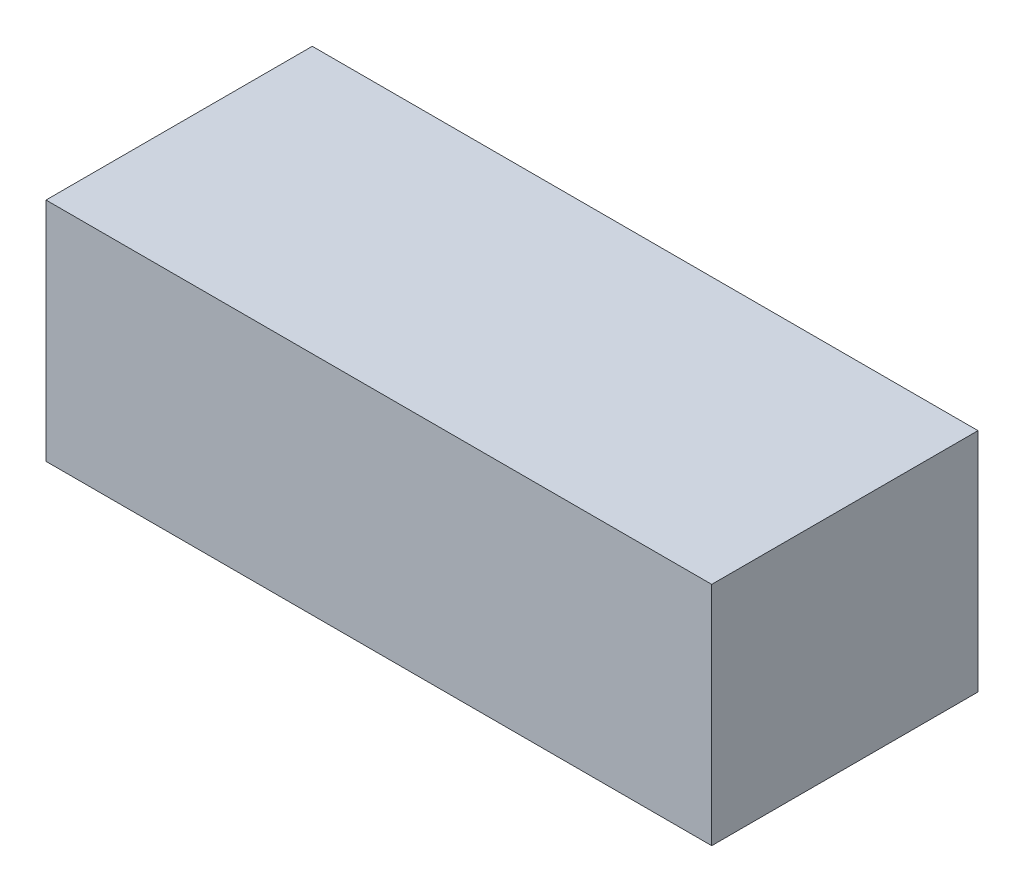
SolidWorks part; units mm, degrees
ref_plane "Front Plane" through (0, 0, 0) normal (0, 0, 1) x (1, 0, 0)
ref_plane "Top Plane" through (0, 0, 0) normal (0, 1, 0) x (1, 0, 0)
ref_plane "Right Plane" through (0, 0, 0) normal (1, 0, 0) x (0, 0, -1)
sketch "Sketch1" plane through (0, 0, 0) normal (0, 1, 0) x (1, 0, 0)
  line L1 (-25, -10) -> (25, -10)
  line L2 (-25, -10) -> (-25, 10)
  line L3 (-25, 10) -> (25, 10)
  line L4 (25, -10) -> (25, 10)
  line L5 (-25, -10) -> (25, 10) construction
  line L6 (-25, 10) -> (25, -10) construction
  point P0 (0, 0)
  dimension "D1" = 50
  dimension "D2" = 20
extrude "Boss-Extrude1" add sketch "Sketch1" along normal blind 17
